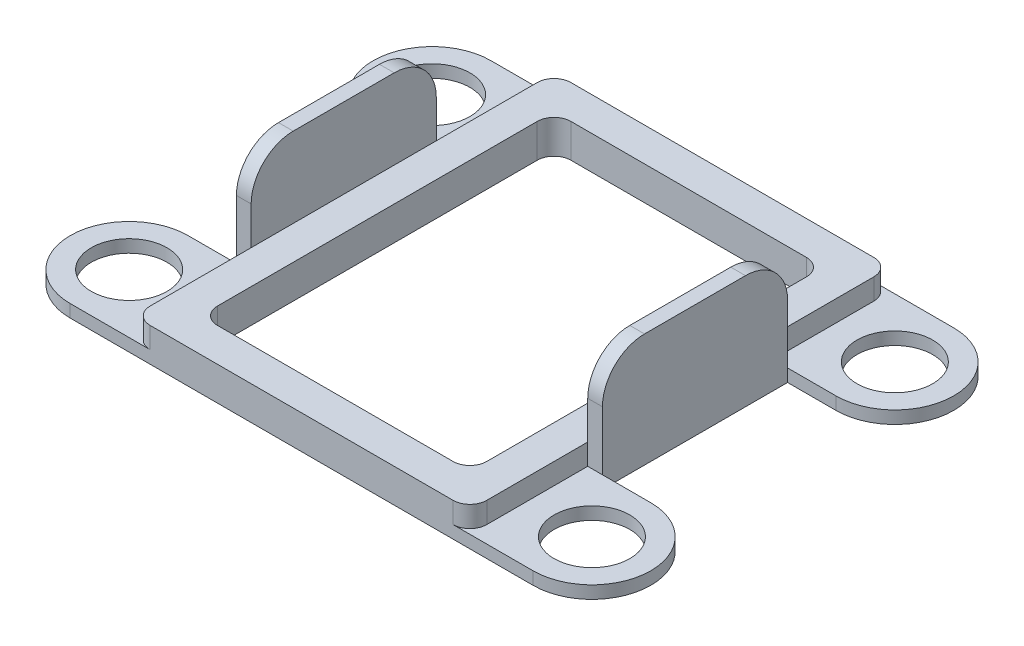
SolidWorks part; units mm, degrees
ref_plane "Front Plane" through (0, 0, 0) normal (0, 0, 1) x (1, 0, 0)
ref_plane "Top Plane" through (0, 0, 0) normal (0, 1, 0) x (1, 0, 0)
ref_plane "Right Plane" through (0, 0, 0) normal (1, 0, 0) x (0, 0, -1)
sketch "Sketch1" plane through (0, 0, 0) normal (0, 1, 0) x (1, 0, 0)
  line L0 (0, 0) -> (0, 28.6926) construction
  line L1 (-27.5, 25) -> (27.5, 25)
  line L2 (27.5, -25) -> (-27.5, -25)
  line L3 (0, 0) -> (21.3554, 0) construction
  line L4 (-21.75, 11) -> (-21.75, -11)
  line L5 (21.75, 11) -> (21.75, -11)
  line L6 (27.5, 11) -> (21.75, 11)
  line L7 (27.5, -11) -> (21.75, -11)
  line L8 (-27.5, -11) -> (-21.75, -11)
  line L9 (-27.5, 11) -> (-21.75, 11)
  circle A0 centre (27.5, 18) radius 4.5
  circle A1 centre (-27.5, 18) radius 4.5
  circle A2 centre (-27.5, -18) radius 4.5
  circle A3 centre (27.5, -18) radius 4.5
  arc A4 (27.5, 11) -> (27.5, 25) centre (27.5, 18) ccw
  arc A5 (-27.5, 25) -> (-27.5, 11) centre (-27.5, 18) ccw
  arc A6 (-27.5, -11) -> (-27.5, -25) centre (-27.5, -18) ccw
  arc A7 (27.5, -25) -> (27.5, -11) centre (27.5, -18) ccw
  point P32 (-27.5, -11)
  point P33 (-27.5, 11)
  dimension "D1" = 9
  dimension "D4" = 2.5
  dimension "D5" = 43.5
  dimension "D2" = 55
  dimension "D3" = 36
extrude "Boss-Extrude1" add sketch "Sketch1" along normal blind 1.5 contours L2 A7 L7 L5 L6 A4 L1 A5 L9 L4 L8 A6 A0 A1 A2 A3 region at (0, 0, 0)
sketch "Sketch2" plane through (0, 1.5, 0) normal (0, 1, 0) x (1, 0, 0)
  line L0 (-21.75, 11) -> (-21.75, -11) construction
  line L1 (-21.75, 11) -> (-20, 11)
  line L2 (-21.75, 11) -> (-21.75, -11)
  line L3 (-21.75, -11) -> (-20, -11)
  line L4 (-20, 11) -> (-20, -11)
  line L5 (-27.5, -11) -> (-21.75, -11) construction
  line L6 (27.5, -11) -> (21.75, -11) construction
  line L7 (21.75, 11) -> (20, 11)
  line L8 (21.75, 11) -> (21.75, -11)
  line L9 (21.75, -11) -> (20, -11)
  line L10 (20, 11) -> (20, -11)
  line L11 (21.75, 11) -> (21.75, -11) construction
  line L12 (0, 0) -> (0, -44.2367) construction
  point P4 (0, -25)
  point P22 (0, -44.2367)
  point P24 (0, 0)
  line M14 (21.75, -11) -> (21.75, 11)
  dimension "D1" = 40
extrude "Boss-Extrude2" add sketch "Sketch2" along normal blind 12 contours L7 L10 L9 M14 | L4 L3 L2 L1 region at (20.875, 1.5, 0)
sketch "Sketch3" plane through (0, 1.5, 0) normal (0, 1, 0) x (1, 0, 0)
  line L0 (-27.5, 25) -> (27.5, 25) construction
  line L1 (-20, 25) -> (20, 25)
  line L2 (-20, 25) -> (-20, -25)
  line L3 (-20, -25) -> (20, -25)
  line L4 (20, 25) -> (20, -25)
  line L5 (27.5, -25) -> (-27.5, -25) construction
  line L6 (20, 11) -> (20, -11) construction
  line L7 (-20, 11) -> (-20, -11) construction
  line L8 (-16, 21) -> (-16, -21)
  line L9 (-16, -21) -> (16, -21)
  line L10 (16, 21) -> (16, -21)
  line L11 (-16, 21) -> (16, 21)
  dimension "D1" = 4
extrude "Boss-Extrude3" add sketch "Sketch3" along normal blind 2.5
extrude "Cut-Extrude1" cut sketch "Sketch3<2>" against normal through all both and the other way through all contours L11 L10 L9 L8
sketch "Sketch3<2>" plane through (0, 1.5, 0) normal (0, 1, 0) x (1, 0, 0) same geometry as "Sketch3"
fillet "Fillet1" radius 2 4 edges at (20, 2.75, -25) (20, 2.75, 25) (-20, 2.75, 25) (-20, 2.75, -25)
fillet "Fillet2" radius 2 4 edges at (-16, 2, 21) (16, 2, 21) (16, 2, -21) (-16, 2, -21)
fillet "Fillet3" radius 5 4 edges at (20.875, 13.5, -11) (20.875, 13.5, 11) (-20.875, 13.5, -11) (-20.875, 13.5, 11)
